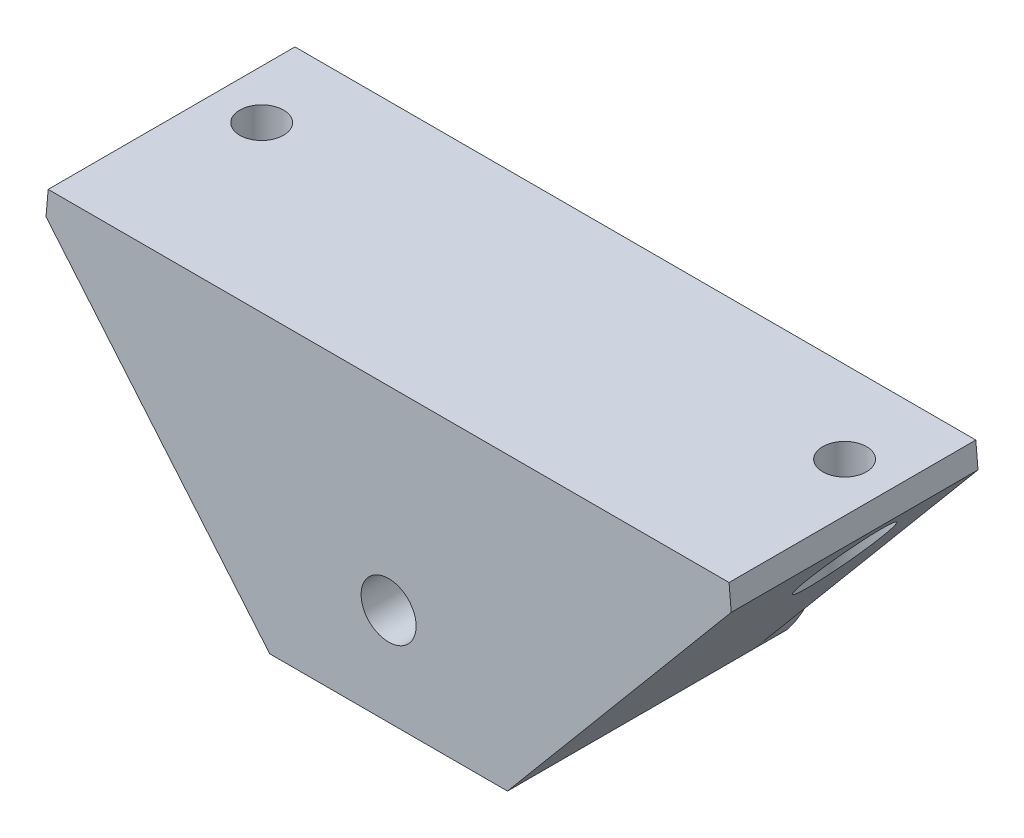
SolidWorks part; units mm, degrees
ref_plane "Front Plane" through (0, 0, 0) normal (0, 0, 1) x (1, 0, 0)
ref_plane "Top Plane" through (0, 0, 0) normal (0, 1, 0) x (1, 0, 0)
ref_plane "Right Plane" through (0, 0, 0) normal (1, 0, 0) x (0, 0, -1)
sketch "Sketch1" plane through (0, 0, 0) normal (0, 0, 1) x (1, 0, 0)
  circle A0 centre (0, 0) radius 15.5
  circle A1 centre (0, 0) radius 18.7
  circle A2 centre (0, 7.5) radius 6.5
  circle A3 centre (0, 0) radius 23.7
  dimension "D1" = 31
  dimension "D2" = 37.4
  dimension "D3" = 13
  dimension "D4" = 7.5
  dimension "D5" = 5
extrude "Boss-Extrude1" add sketch "Sketch1" against normal blind 38.1 contours A3 A1 region at (-23.0297, 0, 0)
extrude "Boss-Extrude2" add sketch "Sketch1<3>" along normal blind 5 contours A3 A1 | A1 A0 | A0 A2 | A2 region at (0, -1.6004, 0) region at (-18.1711, 0, 0) region at (0, 7.5, 0) region at (-23.0297, 0, 0)
sketch "Sketch1<3>" plane through (0, 0, 0) normal (0, 0, 1) x (1, 0, 0) same geometry as "Sketch1"
sketch "Sketch5" plane through (0, 0, 5) normal (0, 0, 1) x (1, 0, 0)
  line L0 (-56.1111, 30) -> (56.1111, 30)
  line L1 (-56.1111, 30) -> (-18.1553, -15.2341)
  line L2 (56.1111, 30) -> (18.1553, -15.2341)
  circle A0 centre (0, 0) radius 23.7 construction
  circle A1 centre (0, 0) radius 23.7
  circle M11 centre (0, 0) radius 23.7
  dimension "D1" = 30
  dimension "D2" = 50
extrude "Boss-Extrude3" add sketch "Sketch5" against normal blind 38.1 contours L2 L0 L1 M11 region at (0, 28.79, 5)
sketch "Sketch6" plane through (0, 30, 0) normal (0, 1, 0) x (1, 0, 0)
  line L0 (-45, 20.4) -> (45, 20.4) construction
  line L2 (-56.1111, -5) -> (56.1111, -5) construction
  point P3 (0, 20.4)
  dimension "D1" = 90
  dimension "D2" = 25.4
hole_wizard "1/4 Clearance Hole1" positions "Sketch7" profile "Sketch8" hole size "1/4" standard "ANSI Inch" end condition through all
sketch "Sketch7" plane through (0, 30, 0) normal (0, 1, 0) x (1, 0, 0)
  point P0 (-45, 20.4)
  point P3 (45, 20.4)
sketch "Sketch8" plane through (-45, 30, -20.4) normal (1, 0, 0) x (0, 0, 1)
  line L0 (0, 0) -> (0, 53.7)
  line L1 (0, 53.7) -> (3.3782, 53.7)
  line L2 (3.3782, 53.7) -> (3.3782, 0)
  line L5 (3.3782, 0) -> (0, 0)
  line L11 (0, -6.35) -> (0, 107.95) construction
  dimension "Thru Hole Dia." = 6.7564
  dimension "Thru Hole Depth" = 53.7
ref_plane "Plane2" through (0, 25, 0) normal (0, 1, 0) x (1, 0, 0)
sketch "Sketch9" plane through (0, 25, 0) normal (0, 1, 0) x (1, 0, 0)
  circle A0 centre (-45, 20.4) radius 5.715
  circle A1 centre (45, 20.4) radius 5.715
  dimension "D1" = 11.43
extrude "Cut-Extrude1" cut sketch "Sketch9" against normal through all
chamfer "Chamfer1" distance 5 angle 45 2 edges at (56.1111, 30, -14.05) (-56.1111, 30, -14.05) first distance on face at (50.715, 23.5691, -20.4) first distance on face at (-50.715, 23.5691, -20.4)
sketch "Sketch10" plane through (0, 0, 0) normal (0, 0, -1) x (-1, 0, 0)
  circle A0 centre (0, 0) radius 18.7 construction
  circle A1 centre (0, 0) radius 18.7
  circle A2 centre (0, 0) radius 4.25
  dimension "D1" = 8.5
extrude "Boss-Extrude4" add sketch "Sketch10" along normal up to surface (38.1 mm away) up to face at (18.7, 0, -38.1)
extrude "Cut-Extrude2" cut sketch "Sketch10<2>" against normal through all contours A2 region at (0, 0, 0)
sketch "Sketch10<2>" plane through (0, 0, 0) normal (0, 0, -1) x (-1, 0, 0) same geometry as "Sketch10"
ref_plane "Plane3" through (0, -23.7, 0) normal (0, -1, 0) x (-1, 0, 0)
sketch "Sketch11" plane through (0, -23.7, 0) normal (0, -1, 0) x (-1, 0, 0)
  line L0 (0, 38.1) -> (0, -5) construction
  line L1 (4.25, 38.1) -> (-4.25, 38.1) construction
  line L2 (-18.1553, -5) -> (18.1553, -5) construction
  circle A0 centre (0, 16.55) radius 2.6
  point P8 (7.7946, 16.6319)
  point P9 (0, 0)
  point P10 (0, 16.55)
  dimension "D1" = 5.2
extrude "Cut-Extrude3" cut sketch "Sketch11" against normal blind 22
ref_plane "Plane4" through (0, -15, 0) normal (0, 1, 0) x (1, 0, 0)
split "Split1" trim tools "Plane4" bodies to split 110 resulting bodies 112
